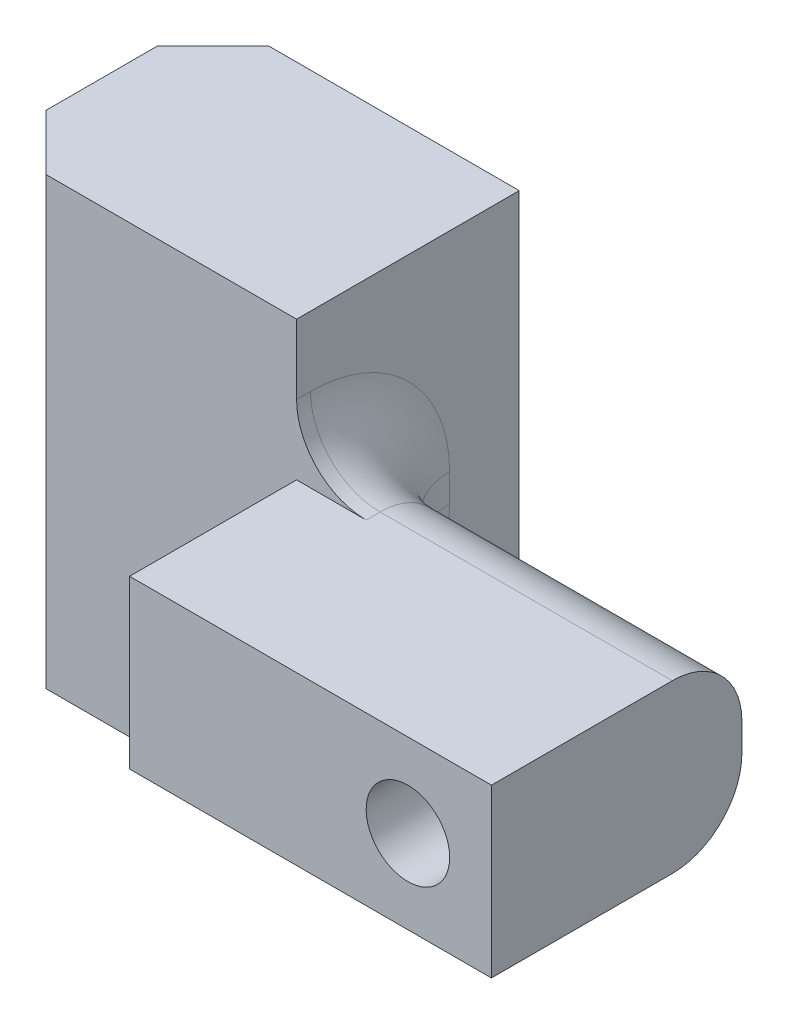
SolidWorks part; units mm, degrees
ref_plane "Plano frontal" through (0, 0, 0) normal (0, 0, 1) x (1, 0, 0)
ref_plane "Plano superior" through (0, 0, 0) normal (0, 1, 0) x (1, 0, 0)
ref_plane "Plano direito" through (0, 0, 0) normal (1, 0, 0) x (0, 0, -1)
sketch "Esboço1" plane through (0, 0, 0) normal (0, 0, 1) x (1, 0, 0)
  line L1 (-3, -3) -> (3, -3)
  line L3 (-3, 3) -> (3, 3)
  line L4 (3, -3) -> (3, 3)
  line L5 (-3, -3) -> (3, 3) construction
  line L6 (-3, 3) -> (3, -3) construction
  line L7 (-3, 3) -> (-10, 3)
  line L9 (-3, -3) -> (-10, -3)
  line L10 (-10, 3) -> (-10, -3)
  circle A0 centre (0, 0) radius 1.5
extrude "Ressalto-extrusão1" add sketch "Esboço1" along normal blind 9
sketch "Esboço2" plane through (0, -3, 0) normal (0, -1, 0) x (1, 0, 0)
  line L2 (-10, 3) -> (-21, 3)
  line L3 (-10, 3) -> (-10, -5)
  line L4 (-10, -5) -> (-21, -5)
  line L5 (-21, 3) -> (-21, -5)
  line L6 (-10, 3) -> (-10, 9) construction
extrude "Ressalto-extrusão2" add sketch "Esboço2" along normal blind 5 and the other way blind 11
fillet "Filete1" radius 2.5 5 edges at (-3.5, 3, 0) (-3.5, -3, 0) (-10, 0, 0) (-10, 3, 1.5) (-10, -3, 1.5)
chamfer "Chanfro1" distance 2 angle 45 2 edges at (-21, 0, -5) (-21, 0, 3)
